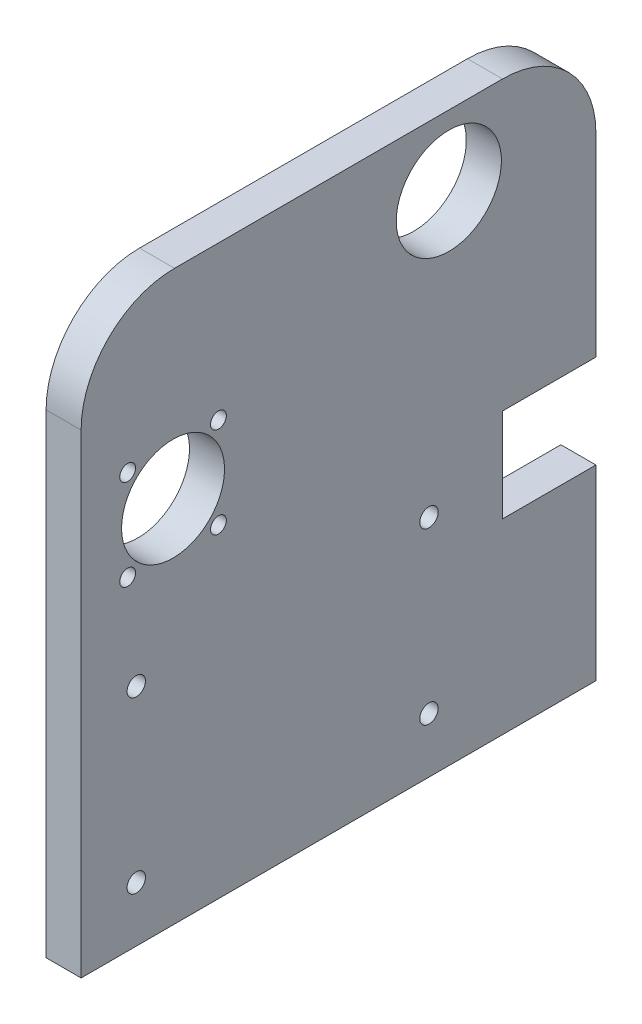
SolidWorks part; units mm, degrees
ref_plane "Front Plane" through (0, 0, 0) normal (0, 0, 1) x (1, 0, 0)
ref_plane "Top Plane" through (0, 0, 0) normal (0, 1, 0) x (1, 0, 0)
ref_plane "Right Plane" through (0, 0, 0) normal (1, 0, 0) x (0, 0, -1)
sketch "Sketch1" plane through (0, 0, 0) normal (0, 1, 0) x (1, 0, 0)
  line L1 (-4.7625, 70) -> (4.7625, 70)
  line L2 (-4.7625, 70) -> (-4.7625, -70)
  line L3 (-4.7625, -70) -> (4.7625, -70)
  line L4 (4.7625, 70) -> (4.7625, -70)
  line L5 (-4.7625, 70) -> (4.7625, -70) construction
  line L6 (-4.7625, -70) -> (4.7625, 70) construction
  point P0 (0, 0)
  dimension "D1" = 140
  dimension "D2" = 9.525
extrude "Boss-Extrude1" add sketch "Sketch1" along normal mid plane 154.4436
fillet "Fillet1" radius 25.4 2 edges at (0, 77.2218, 70) (0, 77.2218, -70)
sketch "Sketch5" plane through (-4.7625, 0, 0) normal (-1, 0, 0) x (0, 0, 1)
  line L1 (-70, 51.8218) -> (-70, -77.2218) construction
  line L2 (-70, -0.9964) -> (-44.6, -0.9964)
  line L3 (-70, -0.9964) -> (-70, -26.3964)
  line L4 (-70, -26.3964) -> (-44.6, -26.3964)
  line L5 (-70, -77.2218) -> (70, -77.2218) construction
  line L6 (-44.6, -0.9964) -> (-44.6, -26.3964)
  dimension "D3" = 25.4
  dimension "D1" = 50.8254
  dimension "D2" = 25.4
sketch "Sketch3" plane through (-4.7625, 0, 0) normal (-1, 0, 0) x (0, 0, 1)
  line L0 (45, 23.1718) -> (61.409, 39.5809) construction
  line L2 (-70, 51.8218) -> (-70, -77.2218) construction
  line L3 (-45.4613, 23.1718) -> (44.137, 23.1718) construction
  line L6 (45, 46.9613) -> (45, -2.4047) construction
  line L7 (-44.6, 77.2218) -> (44.6, 77.2218) construction
  line L8 (70, 51.8218) -> (70, -77.2218) construction
  circle A0 centre (-30, 58.1718) radius 14.29
  circle A1 centre (32.6521, 35.5197) radius 2.15
  circle A2 centre (57.3479, 35.5197) radius 2.15
  circle A3 centre (32.6521, 10.824) radius 2.15
  circle A4 centre (57.3479, 10.824) radius 2.15
  circle A5 centre (45, 23.1718) radius 14
  circle A6 centre (45, 23.1718) radius 17.4625 construction
  dimension "D1" = 28.58
  dimension "D2" = 19.05
  dimension "D3" = 45
  dimension "D4" = 12.3479
  dimension "D7" = 28
  dimension "D8" = 4.3
  dimension "D10" = 35
  dimension "D11" = 25
  dimension "Bolt circle" = 34.925
  dimension "D9" = 40
extrude "Cut-Extrude2" cut sketch "Sketch3" against normal blind 28.575
extrude "Cut-Extrude4" cut sketch "Sketch5" against normal through all
ref_axis "Axis1" through (4.7625, 58.1718, -30) along (-1, 0, 0)
hole_wizard "M6 Tapped Hole1" positions "Sketch7" profile "Sketch6" tap size "M6" standard "DIN"
sketch "Sketch7" plane through (0, 0, -44.6) normal (0, 0, -1) x (-1, 0, 0)
  line L1 (-4.7625, -26.3964) -> (4.7625, -26.3964) construction
  point P0 (0, -13.6964)
  dimension "D1" = 12.7
sketch "Sketch6" plane through (0, -13.6964, -44.6) normal (1, 0, 0) x (0, 1, 0)
  line L0 (0, 0) -> (0, 11.5022)
  line L1 (0, 11.5022) -> (2.5, 10)
  line L2 (2.5, 10) -> (2.5, 0)
  line L5 (2.5, 0) -> (0, 0)
  line L10 (0, 11.5022) -> (-2.5, 10) construction
  line L11 (0, -6.35) -> (0, 107.95) construction
  dimension "Tap Drill Dia." = 5
  dimension "Tap Drill Depth" = 10
  dimension "Drill Angle" = 118
cosmetic thread "Hole Thread1" parameters "D1"=10, "D2"=6
hole_wizard "M6 Tapped Hole2" positions "Sketch9" profile "Sketch8" tap size "M6" standard "DIN" end condition through all
sketch "Sketch9" plane through (-4.7625, 0, 0) normal (-1, 0, 0) x (0, 0, 1)
  line L0 (-44.6, -26.3964) -> (-44.6, -0.9964) construction
  line L1 (-70, -26.3964) -> (-70, -77.2218) construction
  line L2 (70, 51.8218) -> (70, -77.2218) construction
  line L3 (-44.6, -0.9964) -> (-70, -0.9964) construction
  line L5 (-70, -77.2218) -> (70, -77.2218) construction
  point P0 (-24.6, -15.9964)
  point P2 (55, -15.9964)
  point P4 (-24.6, -62.2218)
  point P6 (55, -62.2218)
  dimension "D1" = 20
  dimension "D2" = 45.4
  dimension "D3" = 15
  dimension "D4" = 15
  dimension "D5" = 15
  dimension "D6" = 15
  dimension "D7" = 15
  dimension "D8" = 15
sketch "Sketch8" plane through (-4.7625, -15.9964, -24.6) normal (0, 1, 0) x (0, 0, 1)
  line L0 (0, 0) -> (0, 9.525)
  line L1 (0, 9.525) -> (2.5, 9.525)
  line L2 (2.5, 9.525) -> (2.5, 0)
  line L5 (2.5, 0) -> (0, 0)
  line L11 (0, -6.35) -> (0, 107.95) construction
  dimension "Thru Tap Drill Dia." = 5
  dimension "Thru Tap Drill Depth" = 9.525
cosmetic thread "Hole Thread2" parameters "D2"=6
cosmetic thread "Hole Thread3" parameters "D2"=6
cosmetic thread "Hole Thread4" parameters "D2"=6
cosmetic thread "Hole Thread5" parameters "D2"=6
